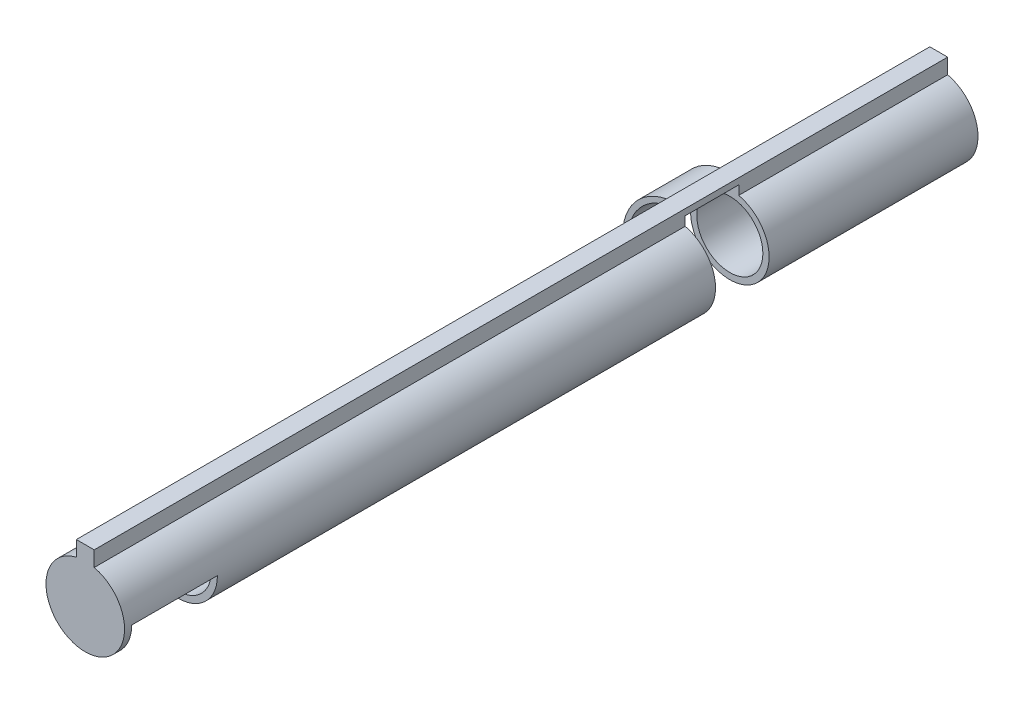
SolidWorks part; units mm, degrees
material "Manual Density from Real Component Plastica Fusoliera"
ref_plane "Piano frontale" through (0, 0, 0) normal (0, 0, 1) x (1, 0, 0)
ref_plane "Piano superiore" through (0, 0, 0) normal (0, 1, 0) x (1, 0, 0)
ref_plane "Piano destro" through (0, 0, 0) normal (1, 0, 0) x (0, 0, -1)
sketch "Schizzo1" plane through (0, 0, 0) normal (0, 0, 1) x (1, 0, 0)
  circle A0 centre (0, 0) radius 9.25
  circle A1 centre (0, 0) radius 11
  dimension "D1" = 18.5
  dimension "D2" = 22
extrude "Tubo" add sketch "Schizzo1" along normal blind 210
sketch "Schizzo2" plane through (0, 0, 210) normal (0, 0, 1) x (1, 0, 0)
  line L0 (0, -9.25) -> (0, -11)
  line L1 (9.25, 0) -> (11, 0)
  arc A0 (11, 0) -> (0, -11) centre (0, 0) ccw
  circle A1 centre (0, 0) radius 11 construction
  arc A2 (0, -9.25) -> (9.25, 0) centre (0, 0) cw
  circle A3 centre (0, 0) radius 9.25 construction
extrude "IngressoCavi" add sketch "Schizzo2" along normal blind 27
sketch "Schizzo4" plane through (0, 0, 210) normal (0, 0, 1) x (1, 0, 0)
  circle A0 centre (0, 0) radius 11
  circle A1 centre (0, 0) radius 6.5
  dimension "D1" = 22
  dimension "D2" = 13
extrude "FondoCorsa" add sketch "Schizzo4" along normal blind 3
sketch "Schizzo5" plane through (0, 0, 237) normal (0, 0, 1) x (1, 0, 0)
  circle A0 centre (0, 0) radius 11
  arc A1 (11, 0) -> (0, -11) centre (0, 0) ccw construction
extrude "Tappo" add sketch "Schizzo5" along normal blind 2
sketch "Schizzo6" plane through (0, 0, 0) normal (0, 0, 1) x (1, 0, 0)
  line L0 (-2.5, 11) -> (-2.5, 15)
  line L5 (2.5, 10.7121) -> (-2.5, 10.7121)
  line L6 (2.5, 10.7121) -> (2.5, 11)
  line L7 (2.5, 11) -> (-2.5, 11) construction
  line L8 (-2.5, 10.7121) -> (-2.5, 11)
  line L9 (-2.5, 15) -> (2.5, 15)
  line L10 (2.5, 15) -> (2.5, 11)
  circle A0 centre (0, 0) radius 11 construction
  point P4 (0, 11)
  dimension "D1" = 4
  dimension "D3" = 5
extrude "BaseInferiore" add sketch "Schizzo6" along normal up to surface (239 mm away) up to face at (11, 0, 239)
ref_plane "PianoFineAnello" through (0, 0, 73.5) normal (0, 0, 1) x (1, 0, 0)
sketch "Schizzo7" plane through (0, 0, 73.5) normal (0, 0, 1) x (1, 0, 0)
  circle A0 centre (0, 0) radius 13.5
  dimension "D1" = 27
extrude "TaglioAnello" cut sketch "Schizzo7" against normal blind 15
sketch "Schizzo8" plane through (0, 0, 73.5) normal (0, 0, 1) x (1, 0, 0)
  line L0 (2.5, 15) -> (-2.5, 15) construction
  line L1 (0, 15) -> (0, 13.5)
  line L2 (-15, 0) -> (-13.5, 0)
  arc A1 (0, 15) -> (-15, 0) centre (0, 0) ccw
  arc A2 (0, 13.5) -> (-13.5, 0) centre (0, 0) ccw
  dimension "D1" = 13.5
extrude "SupportoAnello" add sketch "Schizzo8" against normal blind 15
sketch "Schizzo9" plane through (0, 0, 210) normal (0, 0, -1) x (-1, 0, 0)
  line L0 (-9.25, 0) -> (-11, 0) construction
  line L1 (0, -9.25) -> (0, 0)
  line L2 (0, 0) -> (-9.25, 0)
  arc A0 (0, -9.25) -> (-9.25, 0) centre (0, 0) cw
  circle A1 centre (0, 0) radius 9.25 construction
extrude "FacilitazioneCavi" cut sketch "Schizzo9" against normal up to surface (3 mm away) up to face at (6.5, 0, 213)
fillet "RaccordoFacilitazioneCavi" radius 8 2 edges at (6.5, 0, 211.5) (0, -6.5, 211.5)
